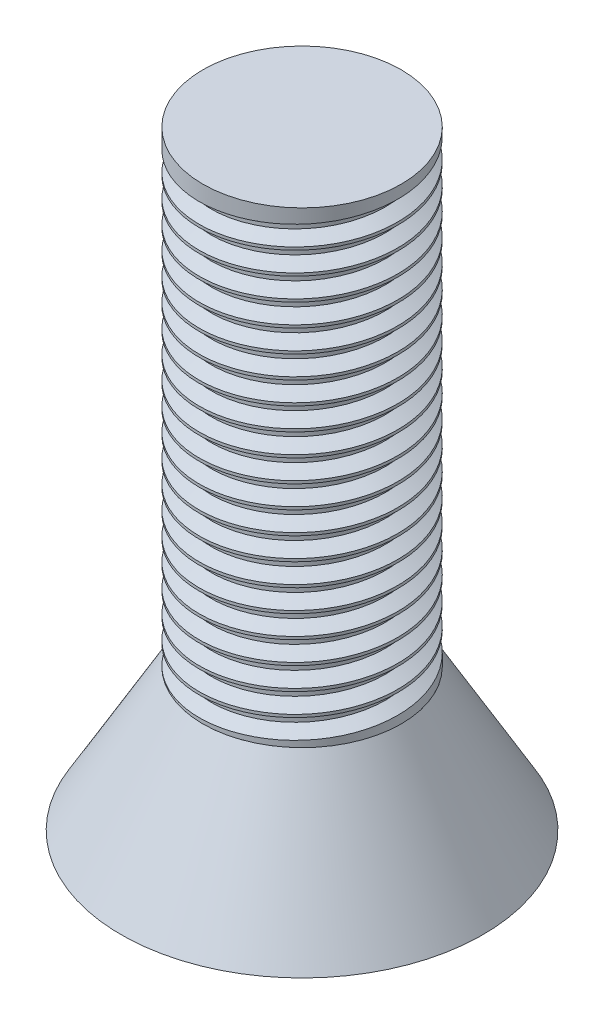
SolidWorks part; units mm, degrees
ref_plane "Alzado" through (0, 0, 0) normal (0, 0, 1) x (1, 0, 0)
ref_plane "Planta" through (0, 0, 0) normal (0, 1, 0) x (1, 0, 0)
ref_plane "Vista lateral" through (0, 0, 0) normal (1, 0, 0) x (0, 0, -1)
sketch "Croquis1" plane through (0, 0, 0) normal (0, 1, 0) x (1, 0, 0)
  circle A1 centre (0, 0) radius 1.4
  dimension "D1" = 2.8
extrude "Saliente-Extruir1" add sketch "Croquis1" along normal blind 3.6
sketch "Croquis5" plane through (0, 0, 0) normal (0, -1, 0) x (1, 0, 0)
  circle A0 centre (0, 0) radius 1.4
extrude "Saliente-Extruir3" add sketch "Croquis5" along normal blind 2 draft 30 separate body draft outward yes
sketch "Croquis6" plane through (0, -2, 0) normal (0, -1, 0) x (1, 0, 0)
  line L0 (-2.5547, 0) -> (-2.2383, 0) construction
  line L1 (0, 2.5547) -> (0, 0.3538) construction
  line L2 (0, 0.3538) -> (0, -0.3538)
  line L3 (-1.3538, 0.3538) -> (-2.2383, 0.3538)
  line L4 (-2.2383, 0.3538) -> (-2.2383, -0.3538)
  line L5 (-2.2383, -0.3538) -> (-1.3538, -0.3538)
  line L7 (0.3538, -0.3538) -> (2.1845, -0.3538)
  line L9 (2.1845, 0.3538) -> (0.3538, 0.3538)
  line L10 (0.3538, 1.3538) -> (0.3538, 2.2383)
  line L11 (-0.3538, 2.2383) -> (-0.3538, 1.3538)
  line L12 (0.3538, 2.2383) -> (-0.3538, 2.2383)
  line L13 (1.3538, -0.3538) -> (2.2383, -0.3538)
  line L14 (2.2383, 0.3538) -> (1.3538, 0.3538)
  line L15 (2.2383, -0.3538) -> (2.2383, 0.3538)
  line L16 (-0.3538, -1.3538) -> (-0.3538, -2.2383)
  line L17 (0.3538, -2.2383) -> (0.3538, -1.3538)
  line L18 (-0.3538, -2.2383) -> (0.3538, -2.2383)
  line L19 (0, -0.3538) -> (0, -2.5547) construction
  line L20 (2.2383, 0) -> (2.5547, 0) construction
  line L21 (-2.2383, 0) -> (2.2383, 0)
  circle A0 centre (0, 0) radius 2.5547 construction
  arc A1 (0.3538, -1.3538) -> (1.3538, -0.3538) centre (1.3538, -1.3538) cw
  arc A2 (0.3538, 1.3538) -> (1.3538, 0.3538) centre (1.3538, 1.3538) ccw
  arc A3 (-0.3538, 1.3538) -> (-1.3538, 0.3538) centre (-1.3538, 1.3538) cw
  arc A4 (-0.3538, -1.3538) -> (-1.3538, -0.3538) centre (-1.3538, -1.3538) ccw
  point P10 (-2.2383, 0)
  point P31 (0, 0)
  dimension "D4" = 1
  dimension "D1" = 0.7076
  dimension "D3" = 1.8845
  dimension "D2" = 4
extrude "Cortar-Extruir1" cut sketch "Croquis6" against normal blind 0.25 contours L11 A3 L3 L4 L21 L15 L14 L9 A2 L10 L12 | A4 L16 L18 L17 A1 L7 L13 L15 L21 L4 L5 region at (0, -2, 0.6742) region at (0, -2, -0.6742)
sketch "Croquis7" plane through (0, 3.6, 0) normal (0, 1, 0) x (1, 0, 0)
  circle A0 centre (0, 0) radius 1.4
extrude "Saliente-Extruir4" add sketch "Croquis7" along normal blind 3
thread "Rosca1" pitch 0.3175 method cut profile "Perfil de rosca2" start angle 0, offset 0, length 6.35, pitch 0.3175, diameter 2.8
ref_plane "Plano2" through (-1.4, 6.6, 0) normal (0, 0, 1) x (-1, 0, 0)
sketch "Perfil de rosca2" plane through (-1.4, 6.6, 0) normal (0, 0, 1) x (-1, 0, 0)
  line L0 (0, 0) -> (0, 0.3175) construction
  line L11 (0, 0) -> (0, 0.2778)
  line L12 (0, 0.2778) -> (-0.1719, 0.1786)
  line L13 (-0.1719, 0.1786) -> (-0.1719, 0.0992)
  line L15 (-0.1719, 0.0992) -> (0, 0)
  line L17 (-0.1719, 0.1389) -> (0, 0.1389) construction
  point P2 (0, 0)
  dimension "Pitch" = 0.3175
  dimension "Profile_Angle" = 60
  dimension "Profile_Land" = 0.0794
  dimension "Profile_Height" = 0.1719
